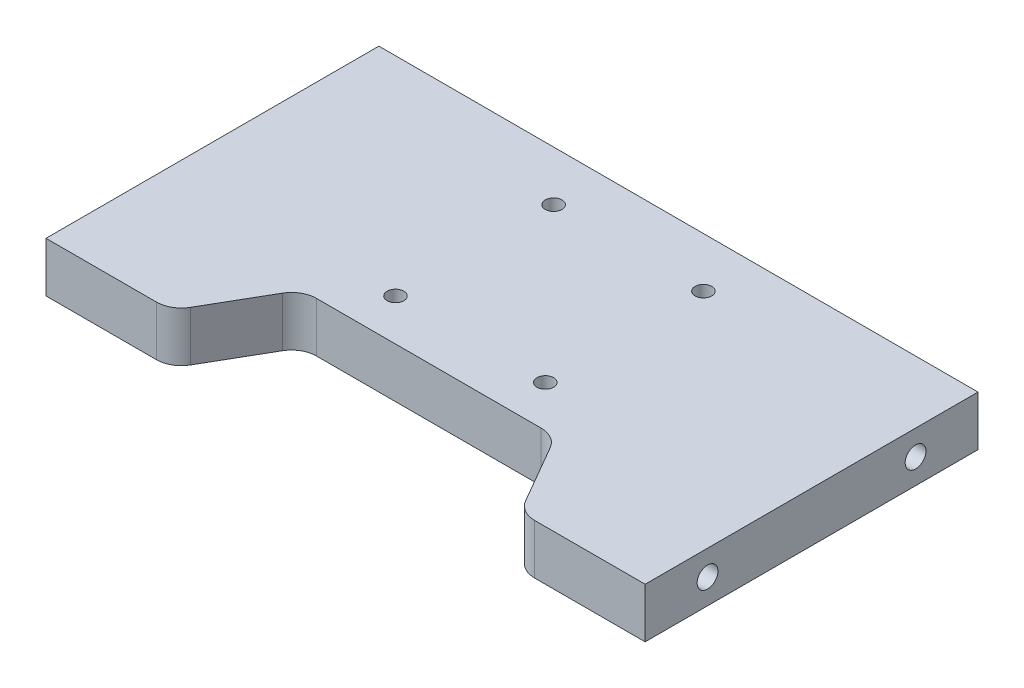
SolidWorks part; units mm, degrees
material "1060 Alloy"
ref_plane "Front Plane" through (0, 0, 0) normal (0, 0, 1) x (1, 0, 0)
ref_plane "Top Plane" through (0, 0, 0) normal (0, 1, 0) x (1, 0, 0)
ref_plane "Right Plane" through (0, 0, 0) normal (1, 0, 0) x (0, 0, -1)
sketch "Sketch1" plane through (0, 0, 0) normal (0, 1, 0) x (1, 0, 0)
  line L1 (0, 0) -> (72, 0)
  line L2 (0, 0) -> (0, 40)
  line L3 (0, 40) -> (72, 40)
  line L4 (72, 0) -> (72, 40)
  dimension "D1" = 72
  dimension "D2" = 40
extrude "Boss-Extrude1" add sketch "Sketch1" along normal blind 6
sketch "Sketch4" plane through (0, 6, 0) normal (0, 1, 0) x (1, 0, 0)
  line L0 (0, 0) -> (72, 0) construction
  line L1 (15, 0) -> (57, 0)
  line L2 (15, 0) -> (20.7735, 10)
  line L3 (20.7735, 10) -> (51.2265, 10)
  line L4 (51.2265, 10) -> (57, 0)
  dimension "D5" = 15
  dimension "D4" = 15
  dimension "D1" = 60
  dimension "D2" = 60
  dimension "D3" = 10
extrude "Cut-Extrude3" cut sketch "Sketch4" against normal up to next
sketch "Sketch5" plane through (0, 6, 0) normal (0, 1, 0) x (1, 0, 0)
  line L0 (51.2265, 10) -> (20.7735, 10) construction
  circle A0 centre (27, 15) radius 1
  circle A1 centre (45, 15) radius 1
  circle A2 centre (45, 34) radius 1
  circle A3 centre (27, 34) radius 1
  dimension "D3" = 2
  dimension "D4" = 5
  dimension "D1" = 18
  dimension "D2" = 19
  dimension "D5" = 27
extrude "Cut-Extrude4" cut sketch "Sketch5" against normal up to next
fillet "Fillet1" radius 3 4 edges at (57, 3, 0) (51.2265, 3, -10) (20.7735, 3, -10) (15, 3, 0)
hole_wizard "Tap Drill for M3 Tap1" positions "Sketch7" profile "Sketch6" hole size "M3" standard "ISO"
sketch "Sketch7" plane through (0, 0, 0) normal (-1, 0, 0) x (0, 0, 1)
  line L0 (0, 6) -> (0, 0) construction
  line L1 (-40, 0) -> (0, 0) construction
  point P0 (-32.5, 3)
  point P2 (-7.5, 3)
  dimension "D1" = 7.5
  dimension "D2" = 25
  dimension "D3" = 3
sketch "Sketch6" plane through (0, 3, -32.5) normal (0, 1, 0) x (0, 0, 1)
  line L0 (0, 0) -> (0, 10.7511)
  line L1 (0, 10.7511) -> (1.25, 10)
  line L2 (1.25, 10) -> (1.25, 0)
  line L5 (1.25, 0) -> (0, 0)
  line L10 (0, 10.7511) -> (-1.25, 10) construction
  line L11 (0, -6.35) -> (0, 107.95) construction
  dimension "Hole Dia." = 2.5
  dimension "Hole Depth" = 10
  dimension "Drill Angle" = 118
hole_wizard "Tap Drill for M3 Tap2" positions "Sketch9" profile "Sketch8" hole size "M3" standard "ISO"
sketch "Sketch9" plane through (72, 0, 0) normal (1, 0, 0) x (0, 0, -1)
  line L0 (0, 6) -> (0, 0) construction
  line L1 (0, 0) -> (40, 0) construction
  point P0 (7.5, 3)
  point P2 (32.5, 3)
  dimension "D1" = 7.5
  dimension "D2" = 25
  dimension "D3" = 3
sketch "Sketch8" plane through (72, 3, -7.5) normal (0, 1, 0) x (0, 0, -1)
  line L0 (0, 0) -> (0, 10.7511)
  line L1 (0, 10.7511) -> (1.25, 10)
  line L2 (1.25, 10) -> (1.25, 0)
  line L5 (1.25, 0) -> (0, 0)
  line L10 (0, 10.7511) -> (-1.25, 10) construction
  line L11 (0, -6.35) -> (0, 107.95) construction
  dimension "Hole Dia." = 2.5
  dimension "Hole Depth" = 10
  dimension "Drill Angle" = 118
